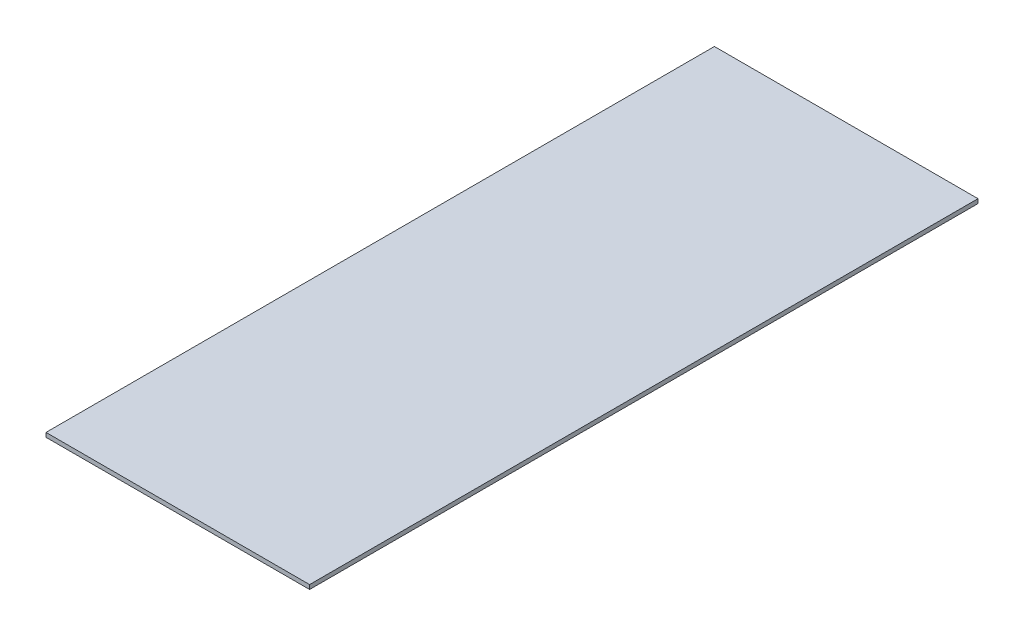
SolidWorks part; units mm, degrees
ref_plane "前视基准面" through (0, 0, 0) normal (0, 0, 1) x (1, 0, 0)
ref_plane "上视基准面" through (0, 0, 0) normal (0, 1, 0) x (1, 0, 0)
ref_plane "右视基准面" through (0, 0, 0) normal (1, 0, 0) x (0, 0, -1)
other "Configuration Table"
sketch "草图1" plane through (0, 0, 0) normal (0, 1, 0) x (1, 0, 0)
  line L1 (-92.53, 234.64) -> (92.53, 234.64)
  line L2 (-92.53, 234.64) -> (-92.53, -234.64)
  line L3 (-92.53, -234.64) -> (92.53, -234.64)
  line L4 (92.53, 234.64) -> (92.53, -234.64)
  line L5 (-92.53, 234.64) -> (92.53, -234.64) construction
  line L6 (-92.53, -234.64) -> (92.53, 234.64) construction
  point P0 (0, 0)
  dimension "D1" = 185.06
  dimension "D2" = 469.28
extrude "凸台-拉伸1" add sketch "草图1" along normal blind 3
